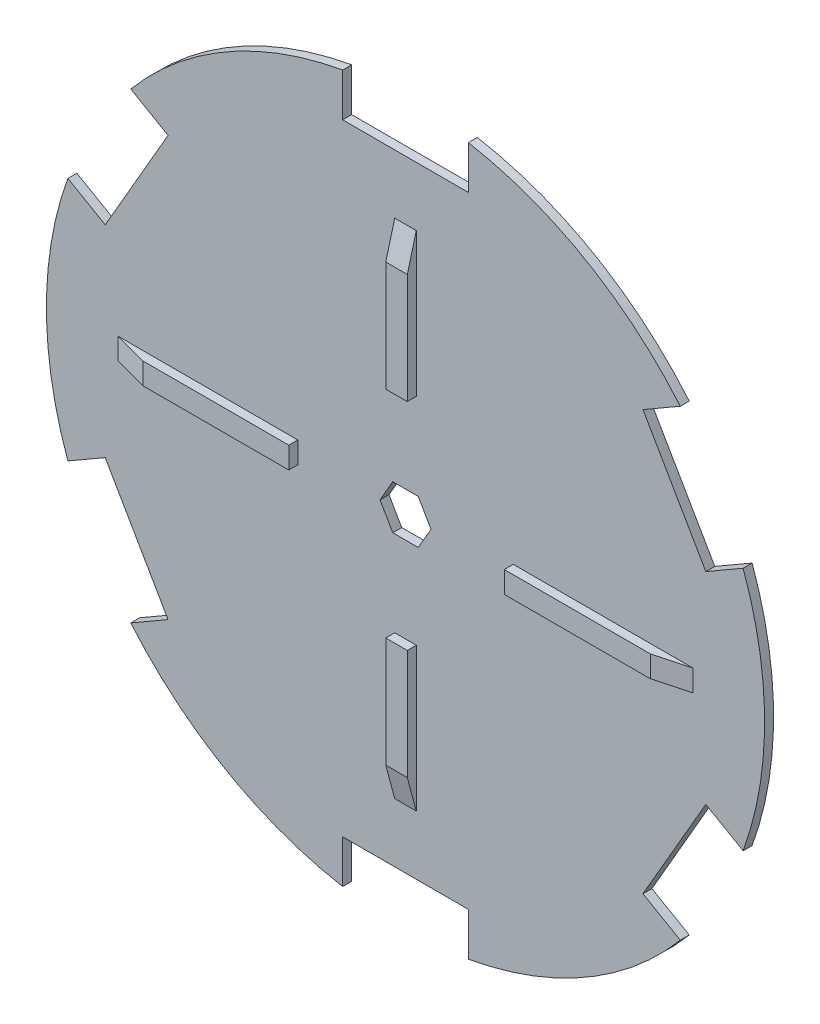
SolidWorks part; units mm, degrees
ref_plane "Front Plane" through (0, 0, 0) normal (0, 0, 1) x (1, 0, 0)
ref_plane "Top Plane" through (0, 0, 0) normal (0, 1, 0) x (1, 0, 0)
ref_plane "Right Plane" through (0, 0, 0) normal (1, 0, 0) x (0, 0, -1)
sketch "Sketch1" plane through (0, 0, 0) normal (0, 0, 1) x (1, 0, 0)
  circle A0 centre (0, 0) radius 100
extrude "Boss-Extrude1" add sketch "Sketch1" along normal blind 2.5 contours A0
sketch "Sketch8" plane through (0, 0, 0) normal (0, 0, -1) x (-1, 0, 0)
  text T0 "02-04-141118"
extrude "Cut-Extrude6" cut sketch "Sketch8" against normal blind 0.2
sketch "Sketch9" plane through (0, 0, 2.5) normal (0, 0, 1) x (1, 0, 0)
  line L1 (-7.1014, 0) -> (-3.5507, -6.15)
  line L2 (-3.5507, -6.15) -> (3.5507, -6.15)
  line L3 (3.5507, -6.15) -> (7.1014, 0)
  line L4 (7.1014, 0) -> (3.5507, 6.15)
  line L5 (3.5507, 6.15) -> (-3.5507, 6.15)
  line L6 (-3.5507, 6.15) -> (-7.1014, 0)
  circle A0 centre (0, 0) radius 6.15 construction
  dimension "D1" = 12.3
extrude "Cut-Extrude7" cut sketch "Sketch9" against normal blind 10
sketch "Sketch11" plane through (0, 0, 2.5) normal (0, 0, 1) x (1, 0, 0)
  line L0 (0, 0) -> (-80, 0)
  line L1 (-80, 0) -> (-80, 3)
  line L2 (-80, 3) -> (-30, 3)
  line L3 (-30, 3) -> (-30, -3)
  line L4 (-30, -3) -> (-80, -3)
  line L5 (-80, -3) -> (-80, 0)
  line L6 (0, 0) -> (0, 70)
  line L7 (0, 70) -> (-3, 70)
  line L8 (-3, 70) -> (-3, 30)
  line L9 (-3, 30) -> (3, 30)
  line L10 (3, 30) -> (3, 70)
  line L11 (3, 70) -> (0, 70)
  line L12 (30, 3) -> (80, 3)
  line L13 (30, -3) -> (30, 3)
  line L14 (80, -3) -> (30, -3)
  line L15 (80, 3) -> (80, 0)
  line L16 (80, 0) -> (80, -3)
  line L17 (3, -30) -> (-3, -30)
  line L18 (3, -70) -> (3, -30)
  line L19 (-3, -30) -> (-3, -70)
  line L20 (0, -70) -> (3, -70)
  line L21 (-3, -70) -> (0, -70)
  point P20 (0, 0)
  point P26 (0, 0)
  dimension "D1" = 3
  dimension "D2" = 6
  dimension "D3" = 6
  dimension "D4" = 3
  dimension "D5" = 80
  dimension "D6" = 50
  dimension "D7" = 70
  dimension "D8" = 40
  dimension "D9" = 2
  dimension "D10" = 2
extrude "Boss-Extrude2" add sketch "Sketch11" along normal blind 2.5 contours L7 L8 L9 L10 L11 | L1 L2 L3 L4 L5 | L14 L13 L12 L15 L16 | L19 L21 L20 L18 L17
chamfer "Chamfer1" distance 2.5 angle 75 4 edges at (80, 0, 5) (0, 70, 5) (0, -70, 5) (-80, 0, 5)
sketch "Sketch12" plane through (0, 0, 2.5) normal (0, 0, 1) x (1, 0, 0)
  line L0 (-83.6238, -28.073) -> (-94.0161, -34.073)
  line L1 (0, -86.4568) -> (-17.5, -86.4568)
  line L2 (-17.5, -86.4568) -> (-17.5, -98.4568)
  line L3 (17.5, -98.4568) -> (17.5, -105.5871)
  line L4 (17.5, -98.4568) -> (17.5, -86.4568)
  line L5 (17.5, -86.4568) -> (0, -86.4568)
  line L6 (17.5, -105.5871) -> (-17.5, -105.5871)
  line L7 (-17.5, -105.5871) -> (-17.5, -98.4568)
  line L8 (-100.1911, -37.6381) -> (-94.0161, -34.073)
  line L9 (-82.6911, -67.949) -> (-100.1911, -37.6381)
  line L10 (-76.5161, -64.3839) -> (-82.6911, -67.949)
  line L11 (-76.5161, -64.3839) -> (-66.1238, -58.3839)
  line L12 (-66.1238, -58.3839) -> (-74.8738, -43.2284)
  line L13 (-74.8738, -43.2284) -> (-83.6238, -28.073)
  line L14 (-66.1238, 58.3839) -> (-76.5161, 64.3839)
  line L15 (-82.6911, 67.949) -> (-76.5161, 64.3839)
  line L16 (-100.1911, 37.6381) -> (-82.6911, 67.949)
  line L17 (-94.0161, 34.073) -> (-100.1911, 37.6381)
  line L18 (-94.0161, 34.073) -> (-83.6238, 28.073)
  line L19 (-83.6238, 28.073) -> (-74.8738, 43.2284)
  line L20 (-74.8738, 43.2284) -> (-66.1238, 58.3839)
  line L21 (17.5, 86.4568) -> (17.5, 98.4568)
  line L22 (17.5, 105.5871) -> (17.5, 98.4568)
  line L23 (-17.5, 105.5871) -> (17.5, 105.5871)
  line L24 (-17.5, 98.4568) -> (-17.5, 105.5871)
  line L25 (-17.5, 98.4568) -> (-17.5, 86.4568)
  line L26 (-17.5, 86.4568) -> (0, 86.4568)
  line L27 (0, 86.4568) -> (17.5, 86.4568)
  line L28 (83.6238, 28.073) -> (94.0161, 34.073)
  line L29 (100.1911, 37.6381) -> (94.0161, 34.073)
  line L30 (82.6911, 67.949) -> (100.1911, 37.6381)
  line L31 (76.5161, 64.3839) -> (82.6911, 67.949)
  line L32 (76.5161, 64.3839) -> (66.1238, 58.3839)
  line L33 (66.1238, 58.3839) -> (74.8738, 43.2284)
  line L34 (74.8738, 43.2284) -> (83.6238, 28.073)
  line L35 (66.1238, -58.3839) -> (76.5161, -64.3839)
  line L36 (82.6911, -67.949) -> (76.5161, -64.3839)
  line L37 (100.1911, -37.6381) -> (82.6911, -67.949)
  line L38 (94.0161, -34.073) -> (100.1911, -37.6381)
  line L39 (94.0161, -34.073) -> (83.6238, -28.073)
  line L40 (83.6238, -28.073) -> (74.8738, -43.2284)
  line L41 (74.8738, -43.2284) -> (66.1238, -58.3839)
  point P46 (0, 0)
  dimension "D1" = 6
  dimension "D2" = 17.5
  dimension "D3" = 17.5
  dimension "D4" = 12
extrude "Cut-Extrude8" cut sketch "Sketch12" against normal blind 10
equation "\"1.5.00mm\"=3"
